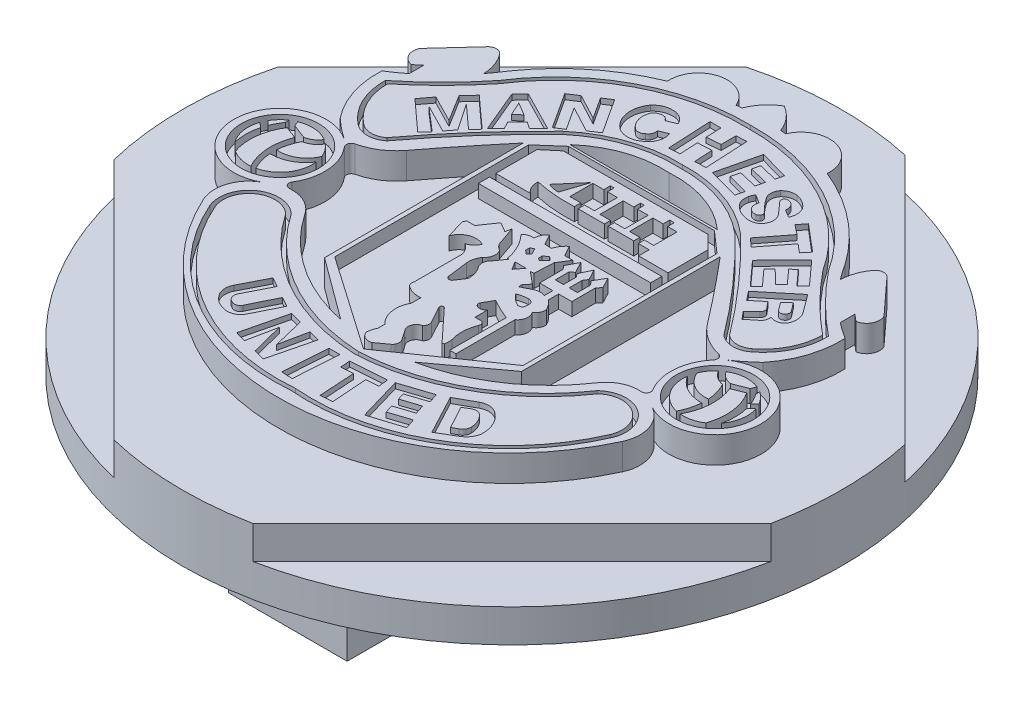
SolidWorks part; units mm, degrees
ref_plane "Ön Düzlem" through (0, 0, 0) normal (0, 0, 1) x (1, 0, 0)
ref_plane "Üst Düzlem" through (0, 0, 0) normal (0, 1, 0) x (1, 0, 0)
ref_plane "Sağ Düzlem" through (0, 0, 0) normal (1, 0, 0) x (0, 0, -1)
sketch "Çizim1" plane through (0, 0, 0) normal (0, 1, 0) x (1, 0, 0)
  line L0 (-150, -150) -> (150, -150)
  line L1 (-150, -150) -> (-150, 150)
  line L2 (-150, 150) -> (150, 150)
  line L3 (150, -150) -> (150, 150)
  line L4 (-150, -150) -> (150, 150) construction
  line L5 (-150, 150) -> (150, -150) construction
  point P0 (0, 0)
  dimension "D1" = 300
  dimension "D2" = 300
extrude "Yükseklik-Ekstrüzyon1" add sketch "Çizim1" along normal blind 35
sketch "Çizim2" plane through (0, 35, 0) normal (0, 1, 0) x (1, 0, 0)
  line L0 (0, 117.0614) -> (0, -131.4053) construction
  line L1 (-110, -110) -> (110, -110) construction
  line L2 (-110, -110) -> (-110, 110) construction
  line L3 (-110, 110) -> (110, 110) construction
  line L4 (110, -110) -> (110, 110) construction
  line L5 (-110, -110) -> (110, 110) construction
  line L6 (-110, 110) -> (110, -110) construction
  line L7 (0, 104.2196) -> (0, 158.9982)
  line L8 (0, 158.9982) -> (174.1845, 158.9982)
  line L9 (174.1845, 158.9982) -> (174.1845, -158.4564)
  line L10 (174.1845, -158.4564) -> (0, -158.4564)
  line L11 (0, -158.4564) -> (0, -87.5)
  line L12 (75.7238, 67.4719) -> (87.9979, 54.073)
  line L13 (84.3468, 47.103) -> (81.7641, 49.2839)
  line L14 (81.7641, 49.2839) -> (81.7641, 43.733)
  arc A0 (73.993, -19.7931) -> (72.5619, 9.9043) centre (82.5, -4.5) ccw
  arc A1 (-61.8718, 61.8718) -> (79.4822, -36.59) centre (0, 0) ccw
  arc A2 (79.4822, -36.59) -> (73.993, -19.7931) centre (67.6734, -31.1538) ccw
  arc A3 (7.3599, 95.5521) -> (9.4064, 95.3805) centre (2.1186, 20.7284) cw
  arc A4 (87.86, 39.4737) -> (81.7641, 43.733) centre (129.197, 105.1277) cw
  arc A5 (87.86, 39.4737) -> (80.1598, 15.9919) centre (53.3041, 37.8019) cw
  arc A6 (80.1598, 15.9919) -> (72.5619, 9.9043) centre (33.8885, 65.9578) cw
  arc A7 (9.4064, 95.3805) -> (30.2904, 90.2439) centre (19.441, 91.1557) cw
  arc A8 (0, 104.2196) -> (7.3599, 95.5521) centre (-8.4138, 89.6166) cw
  arc A9 (30.2904, 90.2439) -> (63.6389, 63.6389) centre (2.1186, 20.7284) cw
  arc A10 (67.6734, 57.8621) -> (70.963, 67.2595) centre (83.7021, 57.5257) cw
  arc A11 (70.963, 67.2595) -> (75.7238, 67.4719) centre (73.4323, 65.3728) cw
  arc A12 (87.9979, 54.073) -> (84.3468, 47.103) centre (83.5011, 51.9873) cw
  arc A13 (67.6734, 57.8621) -> (63.6389, 63.6389) centre (129.197, 105.1277) cw
  point P0 (0, 0)
  line M1 (150, -150) -> (150, 150)
  line M2 (150, 150) -> (-150, 150)
  line M4 (-150, -150) -> (150, -150)
  dimension "D5" = 35
  dimension "D6" = 175
  dimension "D7" = 26
  dimension "D1" = 220
  dimension "D2" = 220
  dimension "D3" = 4.5
  dimension "D4" = 82.5
extrude "Kes-Ekstrüzyon1" cut sketch "Çizim2" against normal blind 10 contours A13 A10 A11 L12 A12 L13 L14 A4 A5 A6 A0 A2 A1 L11 L7 A8 A3 A7 A9 M4 M1 M2 region at (3.3541, 35, -127.1098)
sketch "Çizim3" plane through (0, 35, 0) normal (0, 1, 0) x (1, 0, 0)
  line L0 (0, 60.4845) -> (0, 50.9362)
  line L1 (0, 50.9362) -> (27.9296, 50.9362)
  line L2 (37.3488, 42.6127) -> (37.3488, -32.762)
  line L3 (37.3488, -32.762) -> (13.9496, -50.0197)
  arc A0 (0, 60.4845) -> (27.9296, 50.9362) centre (2.6764, 22.691) cw
  arc A1 (55.2285, -22.4328) -> (13.9496, -50.0197) centre (0.3434, 15.0162) cw
  arc A2 (55.2285, -22.4328) -> (66.7327, -16.6811) centre (65.7274, -29.0514) cw
  arc A3 (69.9632, 7.3871) -> (68.9572, 10.393) centre (68.5479, 8.5847) ccw
  arc A4 (68.9572, 10.393) -> (57.05, 18.0417) centre (73.5332, 30.6092) cw
  arc A5 (37.3488, 42.6127) -> (57.05, 18.0417) centre (-455.6549, -372.867) cw
  arc A6 (66.7327, -16.6811) -> (68.3571, -14.0306) centre (66.8738, -14.9445) ccw
  arc A7 (68.3571, -14.0306) -> (69.9632, 7.3871) centre (83.9275, -4.4291) cw
extrude "Kes-Ekstrüzyon2" cut sketch "Çizim3" against normal blind 10
sketch "Çizim4" plane through (0, 35, 0) normal (0, 1, 0) x (1, 0, 0)
  line L0 (82.5, 1.0789) -> (87.1593, 2.8819)
  line L1 (80.9674, 2.8819) -> (86.3529, 4.9659)
  line L2 (86.3529, 4.9659) -> (87.1074, 6.8198)
  line L3 (89.2335, 4.222) -> (89.2335, 5.6993)
  line L4 (91.5097, 0) -> (93.0987, 1.5854)
  line L5 (92.2018, -2.119) -> (94.0821, -0.5988)
  arc A0 (70.3824, -2.9093) -> (79.7575, -16.4098) centre (82.5, -4.5) ccw
  circle A1 centre (82.5, -4.5) radius 14.6888
  arc A2 (79.7575, 1.0789) -> (81.8823, -6.409) centre (63.1981, -7.6655) cw
  arc A3 (79.7575, 1.0789) -> (74.5498, 4.7822) centre (80.9674, 8.2935) cw
  arc A4 (80.9674, 2.8819) -> (76.2386, 5.9957) centre (81.6657, 9.0899) cw
  arc A5 (81.8823, -6.409) -> (71.1371, 0) centre (80.8034, 3.9943) cw
  arc A6 (81.8823, -8.922) -> (70.3824, -2.9093) centre (81.4328, 4.222) cw
  arc A7 (82.5, 1.0789) -> (81.4038, -16.6723) centre (63.395, -6.6508) cw
  arc A8 (87.1593, 2.8819) -> (89.2335, -14.6993) centre (70.2409, -8.027) cw
  arc A9 (89.2335, 4.222) -> (91.5097, 0) centre (73.1727, -7.1617) cw
  arc A10 (81.8823, -8.922) -> (79.7575, -16.4098) centre (63.1981, -7.6655) cw
  arc A11 (92.2018, -2.119) -> (92.3057, -11.7947) centre (73.1727, -7.1617) cw
  arc A12 (92.3057, -11.7947) -> (94.0821, -0.5988) centre (82.5, -4.5) ccw
  arc A13 (81.4038, -16.6723) -> (89.2335, -14.6993) centre (82.5, -4.5) ccw
  arc A14 (74.5498, 4.7822) -> (71.1371, 0) centre (82.5, -4.5) ccw
  arc A15 (87.1074, 6.8198) -> (76.2386, 5.9957) centre (82.5, -4.5) ccw
  arc A16 (93.0987, 1.5854) -> (89.2335, 5.6993) centre (82.5, -4.5) ccw
extrude "Kes-Ekstrüzyon3" cut sketch "Çizim4" against normal blind 5
sketch "Çizim5" plane through (0, 35, 0) normal (0, 1, 0) x (1, 0, 0)
  line L0 (0, 91.5379) -> (0, 90.0374)
  line L1 (0, 65.6317) -> (0, 64.1304)
  line L2 (0, -57.1722) -> (0, -58.6739)
  line L3 (0, -81.2023) -> (0, -82.7077)
  arc A0 (0, 91.5379) -> (62.5307, 58.4876) centre (1.8857, 19.4269) cw
  arc A1 (84.0268, 36.9915) -> (62.5307, 58.4876) centre (173.773, 148.2339) cw
  arc A2 (84.0268, 36.9915) -> (74.573, 17.2499) centre (59.8349, 36.4421) cw
  arc A3 (74.573, 17.2499) -> (63.8811, 17.4485) centre (69.3515, 24.0494) cw
  arc A4 (0, 64.1304) -> (32.7048, 52.8449) centre (2.0165, 16.9426) cw
  arc A5 (32.7048, 52.8449) -> (63.8811, 17.4485) centre (-172.9235, -159.6954) cw
  arc A6 (0, 90.0374) -> (61.3126, 57.6086) centre (1.8857, 19.4269) cw
  arc A7 (82.5324, 36.2721) -> (61.3126, 57.6086) centre (173.773, 148.2339) cw
  arc A8 (82.5324, 36.2721) -> (73.6594, 18.4396) centre (59.8349, 36.4421) cw
  arc A9 (73.6594, 18.4396) -> (64.9701, 18.4968) centre (69.3515, 24.0494) cw
  arc A10 (33.7148, 53.9549) -> (64.9701, 18.4968) centre (-172.9235, -159.6954) cw
  arc A11 (0, 65.6317) -> (33.7148, 53.9549) centre (2.0165, 16.9426) cw
  arc A12 (58.0281, -24.6994) -> (0, -57.1722) centre (-3.5058, 17.1762) cw
  arc A13 (58.0281, -24.6994) -> (76.3367, -37.159) centre (65.8248, -32.9241) cw
  arc A14 (76.3367, -37.159) -> (0, -82.7077) centre (6.3669, -6.6362) cw
  arc A15 (59.1734, -25.6822) -> (0, -58.6739) centre (-3.5058, 17.1762) cw
  arc A16 (59.1734, -25.6822) -> (74.953, -36.5793) centre (65.8248, -32.9241) cw
  arc A17 (74.953, -36.5793) -> (0, -81.2023) centre (6.3669, -6.6362) cw
extrude "Kes-Ekstrüzyon4" cut sketch "Çizim5" against normal blind 5
mirror "Aynalama1" about plane through (0, 0, 0) normal (1, 0, 0) of "Kes-Ekstrüzyon4", "Kes-Ekstrüzyon3", "Kes-Ekstrüzyon2", "Kes-Ekstrüzyon1"
sketch "Çizim6" plane through (0, 35, 0) normal (0, 1, 0) x (1, 0, 0)
  line L1 (35.6973, -30.5495) -> (35.6973, 43.0345)
  line L2 (35.6973, 43.0345) -> (27.6949, 50.073)
  line L3 (27.6949, 50.073) -> (-27.6949, 50.073)
  line L4 (0, 0) -> (0, 50.073) construction
  line L5 (-35.6973, -30.5495) -> (-35.6973, 43.0345)
  line L6 (-35.6973, 43.0345) -> (-27.6949, 50.073)
  line L7 (-32.5816, 27.4101) -> (-32.5816, 43.0345)
  line L8 (-32.5816, 43.0345) -> (-27.1175, 47.6129)
  line L9 (-27.1175, 47.6129) -> (27.6949, 47.6129)
  line L10 (27.6949, 47.6129) -> (32.7594, 42.5484)
  line L11 (32.7594, 42.5484) -> (32.7594, 27.4101)
  line L12 (32.7594, 27.4101) -> (21.6068, 27.4101)
  line L13 (21.6068, 27.4101) -> (21.6068, 31.3958)
  line L14 (21.6068, 31.3958) -> (17.4791, 31.3958)
  line L15 (17.4791, 31.3958) -> (17.4791, 33.7073)
  line L16 (17.4791, 33.7073) -> (21.0289, 33.7073)
  line L17 (21.0289, 33.7073) -> (21.0289, 42.5484)
  line L18 (21.0289, 42.5484) -> (17.4791, 42.5484)
  line L19 (17.4791, 42.5484) -> (17.4791, 45.0807)
  line L20 (17.4791, 45.0807) -> (15.7454, 45.0807)
  line L21 (15.7454, 45.0807) -> (15.7454, 42.5484)
  line L22 (15.7454, 42.5484) -> (11.8654, 42.5484)
  line L23 (11.8654, 42.5484) -> (11.8654, 33.7073)
  line L24 (11.8654, 33.7073) -> (15.7454, 33.7073)
  line L25 (15.7454, 33.7073) -> (15.7454, 31.3958)
  line L26 (15.7454, 31.3958) -> (6.0866, 31.3958)
  line L27 (6.0866, 31.3958) -> (6.0866, 33.7073)
  line L28 (6.0866, 33.7073) -> (10.0766, 33.7073)
  line L29 (10.0766, 33.7073) -> (10.0766, 42.5484)
  line L30 (10.0766, 42.5484) -> (6.0866, 42.5484)
  line L31 (6.0866, 42.5484) -> (6.0866, 45.0807)
  line L32 (6.0866, 45.0807) -> (4.6191, 45.0807)
  line L33 (4.6191, 45.0807) -> (4.6191, 42.5484)
  line L34 (4.6191, 42.5484) -> (0.626, 42.5484)
  line L35 (0.626, 42.5484) -> (0.626, 33.9856)
  line L36 (0.626, 33.9856) -> (0.626, 33.7073)
  line L37 (0.626, 33.7073) -> (4.6191, 33.7073)
  line L38 (4.6191, 33.7073) -> (4.6191, 31.3958)
  line L39 (4.6191, 31.3958) -> (-5.3406, 31.3958)
  line L40 (-5.3406, 31.3958) -> (-5.3406, 33.8465)
  line L41 (-5.3406, 33.8465) -> (-1.577, 33.8465)
  line L42 (-1.577, 33.8465) -> (-1.577, 42.5484)
  line L43 (-1.577, 42.5484) -> (-5.3406, 42.5484)
  line L44 (-5.3406, 42.5484) -> (-5.3406, 45.0807)
  line L45 (-5.3406, 45.0807) -> (-6.7635, 45.0807)
  line L46 (-6.7635, 45.0807) -> (-6.7635, 42.5484)
  line L47 (-6.7635, 42.5484) -> (-10.8942, 42.5484)
  line L48 (-10.8942, 42.5484) -> (-10.8942, 33.8465)
  line L49 (-10.8942, 33.8465) -> (-6.7635, 33.8465)
  line L50 (-6.7635, 33.8465) -> (-6.7635, 31.3958)
  line L51 (-32.5816, 27.4101) -> (-19.4372, 27.4101)
  line L52 (-18.8002, 33.9856) -> (-11.4217, 42.5484)
  line L53 (-11.4217, 42.5484) -> (-14.5776, 33.1488)
  line L54 (-20.9353, -1.9012) -> (-23.028, 5.1542)
  line L55 (-32.5816, 25.0346) -> (32.7594, 25.0346)
  line L56 (-32.5816, 25.0346) -> (-32.5816, 20.8236)
  line L57 (-32.5816, 20.8236) -> (32.7594, 20.8236)
  line L58 (32.7594, 25.0346) -> (32.7594, 20.8236)
  line L59 (-23.028, 5.1542) -> (-22.4899, 6.2902)
  line L60 (-22.4899, 6.2902) -> (-19.4372, 6.2902)
  line L61 (-19.4372, 6.2902) -> (-15.3747, 12.1497)
  line L62 (-15.3747, 12.1497) -> (-11.7302, 10.0129)
  line L63 (-11.7302, 10.0129) -> (-11.2545, 12.1497)
  line L64 (-11.2545, 12.1497) -> (-8.7396, 4.8729)
  line L65 (-8.7396, -7.5608) -> (-7.7318, -15.1699)
  line L66 (-5.5404, -15.7177) -> (-3.3186, -12.4306)
  line L67 (-4.5097, -2.0077) -> (-1.8177, 1.8177)
  line L68 (-1.8177, 1.8177) -> (-2.4508, 1.8177)
  line L69 (-2.2142, 17.4209) -> (0, 13.4692)
  line L70 (0, 13.4692) -> (2.5928, 13.3318)
  line L71 (5.3491, 17.4209) -> (7.4713, 13.4692)
  line L72 (7.4713, 13.4692) -> (10.6011, 13.4692)
  line L73 (10.6011, 13.4692) -> (7.8603, 9.1968)
  line L74 (7.8603, 9.1968) -> (7.4713, 1.8177)
  line L75 (7.4713, 1.8177) -> (6.0866, 1.8177)
  line L76 (6.0866, 1.8177) -> (10.7337, -2.0077)
  line L77 (10.7337, -2.0077) -> (9.0154, -4.0951)
  line L78 (9.1527, -5.4691) -> (12.5683, -3.7017)
  line L79 (16.7607, -3.5331) -> (16.7607, -0.2789)
  line L80 (16.7607, -0.2789) -> (11.7213, -0.2789)
  line L81 (11.7213, -0.2789) -> (11.7213, 8.6628)
  line L82 (11.7213, 8.6628) -> (10.6011, 10.0129)
  line L83 (10.6011, 10.0129) -> (12.8268, 14.2738)
  line L84 (12.8268, 14.2738) -> (15.0316, 10.0129)
  line L85 (15.0316, 10.0129) -> (13.6782, 8.8901)
  line L86 (13.6782, 8.8901) -> (13.6782, 3.7222)
  line L87 (13.6782, 3.7222) -> (16.7626, 3.7222)
  line L88 (16.7626, 3.7222) -> (16.7626, 8.6619)
  line L89 (16.7626, 8.6619) -> (15.7474, 9.8855)
  line L90 (15.7474, 9.8855) -> (17.8609, 14.2728)
  line L91 (17.8609, 14.2728) -> (19.9544, 10.2271)
  line L92 (19.9544, 10.2271) -> (18.9502, 8.6619)
  line L93 (18.9502, 8.6619) -> (18.9502, 3.7222)
  line L94 (18.9502, 3.7222) -> (22.0786, 3.7222)
  line L95 (22.0786, 3.7222) -> (22.0786, 8.6619)
  line L96 (22.0786, 8.6619) -> (20.78, 10.2271)
  line L97 (20.78, 10.2271) -> (23.1519, 14.2728)
  line L98 (23.1519, 14.2728) -> (25.2454, 10.2271)
  line L99 (25.2454, 10.2271) -> (23.9569, 8.6619)
  line L100 (23.9569, 8.6619) -> (23.9569, -0.2789)
  line L101 (23.9569, -0.2789) -> (18.9502, -0.2789)
  line L102 (18.9502, -0.2789) -> (18.9502, -4.0951)
  line L103 (19.1333, -16.9923) -> (19.1333, -39.3968)
  line L104 (19.1333, -39.3968) -> (16.7845, -39.3968)
  line L105 (16.7845, -39.3968) -> (16.7845, -18.0047)
  line L106 (9.1527, -14.3283) -> (7.0465, -18.0047)
  line L107 (10.7336, -18.9486) -> (10.7336, -23.7673)
  line L108 (10.7336, -23.7673) -> (12.903, -23.7673)
  line L109 (12.7472, -38.2908) -> (1.7423, -26.4215)
  line L110 (0.626, -27.3608) -> (3.9137, -33.388)
  line L111 (2.0023, -41.7035) -> (4.3504, -45.1697)
  line L112 (3.7012, -48.5626) -> (-0.5329, -51.6429)
  line L113 (-4.0678, -45.8128) -> (-4.0678, -43.1848)
  line L114 (-5.9442, -31.2079) -> (-5.9442, -27.6327)
  line L115 (-12.4124, -23.7185) -> (-12.4124, -5.4691)
  line L116 (0, -55.3459) -> (-35.6973, -30.5495)
  line L117 (0, -55.3459) -> (35.6973, -30.5495)
  arc A0 (-6.7635, 31.3958) -> (-21.732, 32.6211) centre (-9.7576, 86.8596) cw
  arc A1 (-19.4372, 27.4101) -> (-21.732, 32.6211) centre (-15.9804, 32.0431) cw
  arc A2 (-14.5776, 33.1488) -> (-18.8002, 33.9856) centre (-14.9068, 42.5604) cw
  arc A3 (-20.9353, -1.9012) -> (-11.9069, 1.5667) centre (-14.8859, -4.164) cw
  arc A4 (-6.5727, 2.8365) -> (-8.7396, 4.8729) centre (-3.5561, 8.2174) cw
  arc A5 (-6.5727, 2.8365) -> (-7.4893, -2.6815) centre (-9.9894, 0.5689) cw
  arc A6 (-8.7396, -7.5608) -> (-7.4893, -2.6815) centre (-1.3306, -6.8595) cw
  arc A7 (-5.5404, -15.7177) -> (-7.7318, -15.1699) centre (-6.5681, -15.1718) cw
  arc A8 (-4.9621, -6.8595) -> (-3.3186, -12.4306) centre (-12.0993, -11.9931) cw
  arc A9 (-4.9621, -6.8595) -> (-4.5097, -2.0077) centre (-2.2142, -4.6688) cw
  arc A10 (-7.7318, 12.1497) -> (-2.4508, 1.8177) centre (-22.8138, -2.0749) cw
  arc A11 (-7.7318, 12.1497) -> (-4.0678, 13.3318) centre (-4.9068, 9.6627) cw
  arc A12 (-4.0678, 13.3318) -> (-2.2142, 17.4209) centre (1.0663, 13.4692) cw
  arc A13 (2.5928, 13.3318) -> (5.3491, 17.4209) centre (10.7337, 10.8179) cw
  arc A14 (9.1527, -5.4691) -> (9.0154, -4.0951) centre (10.0604, -4.6845) cw
  arc A15 (12.5683, -3.7017) -> (16.7607, -3.5331) centre (14.8448, -8.1009) cw
  arc A16 (18.9502, -4.0951) -> (21.7977, -7.8033) centre (11.8908, -12.4633) cw
  arc A17 (21.7977, -7.8033) -> (19.9544, -11.2995) centre (18.1521, -8.1153) cw
  arc A18 (19.9544, -11.2995) -> (19.1333, -16.9923) centre (16.7845, -13.7479) cw
  arc A19 (16.7845, -18.0047) -> (9.1527, -14.3283) centre (38.6907, 37.2295) cw
  arc A20 (10.7336, -18.9486) -> (7.5006, -19.6804) centre (8.7332, -17.6184) cw
  arc A21 (7.5006, -19.6804) -> (7.0465, -18.0047) centre (8.1422, -18.6071) cw
  arc A22 (12.903, -23.7673) -> (14.0714, -25.8765) centre (12.7472, -25.2318) cw
  arc A23 (13.6782, -35.3875) -> (14.0714, -25.8765) centre (27.8055, -31.2079) cw
  arc A24 (13.6782, -35.3875) -> (13.6782, -38.2908) centre (5.8594, -36.8392) cw
  arc A25 (13.6782, -38.2908) -> (12.7472, -38.2908) centre (13.2127, -37.7367) cw
  arc A26 (0.626, -27.3608) -> (1.7423, -26.4215) centre (1.2795, -27.0044) cw
  arc A27 (3.9137, -33.388) -> (3.4928, -36.4976) centre (2.0023, -34.7126) cw
  arc A28 (2.0023, -41.7035) -> (3.4928, -36.4976) centre (4.1169, -39.4926) cw
  arc A29 (4.3504, -45.1697) -> (3.7012, -48.5626) centre (2.215, -46.5197) cw
  arc A30 (-0.5329, -51.6429) -> (-4.9621, -49.3989) centre (-1.5866, -48.2296) cw
  arc A31 (-4.9621, -49.3989) -> (-4.0678, -45.8128) centre (2.6395, -49.39) cw
  arc A32 (-4.0678, -43.1848) -> (-5.9442, -31.2079) centre (2.7587, -35.9799) cw
  arc A33 (-5.9442, -27.6327) -> (-11.7277, -26.0886) centre (-6.9517, -19.8036) cw
  arc A34 (-11.7277, -26.0886) -> (-12.4124, -23.7185) centre (-10.4776, -24.4435) cw
  arc A35 (-15.3747, -1.4858) -> (-12.4124, -5.4691) centre (-18.869, -7.1776) cw
  arc A36 (-11.9069, 1.5667) -> (-15.3747, -1.4858) centre (-16.2343, 2.9868) cw
extrude "Kes-Ekstrüzyon5" cut sketch "Çizim6" against normal blind 5 contours A36 A3 L54 L59 L60 L61 L62 L63 L64 A4 A5 A6 L65 A7 L66 A8 A9 L67 L68 A10 A11 A12 L69 L57 L56 L55 L39 L40 L41 L42 L43 L44 L45 L46 L47 L48 L49 L50 A0 A1 L51 L7 L8 L9 L3 L6 L5 L116 | A2 L53 L52 region at (17.1223, 35, 41.902) region at (-14.9914, 35, -36.4596)
sketch "Çizim7" plane through (0, 35, 0) normal (0, 1, 0) x (1, 0, 0)
  line L0 (0.7036, 7.8454) -> (-0.3865, 10.0256)
  line L1 (-0.3865, 10.0256) -> (-1.6945, 9.3715)
  line L2 (-1.6945, 9.3715) -> (-1.6945, 7.8454)
  line L3 (-1.6945, 7.8454) -> (-0.3865, 6.7554)
  line L4 (-0.3865, 6.7554) -> (0.7036, 7.8454)
  line L5 (3.3409, 9.0761) -> (3.3409, 7.6344)
  line L6 (3.3409, 7.6344) -> (4.3606, 7.0015)
  line L7 (4.3606, 7.0015) -> (6.2946, 9.0761)
  line L8 (6.2946, 9.0761) -> (4.9904, 10.292)
  line L9 (4.9904, 10.292) -> (3.3409, 9.0761)
  line L10 (16.742, -8.8134) -> (16.742, -10.7481)
  line L11 (0.1374, 1.9898) -> (4.3606, 1.9898)
  line L12 (4.3606, 1.9898) -> (2.0006, -1.0407)
  line L13 (2.0006, -1.0407) -> (0.1374, 1.9898)
  arc A0 (10.7975, -8.3839) -> (14.8705, -7.5365) centre (15.1195, -18.945) cw
  arc A1 (14.8705, -7.5365) -> (16.742, -8.8134) centre (14.913, -9.4841) cw
  arc A2 (16.742, -10.7481) -> (14.553, -11.6091) centre (15.2849, -10.2569) cw
  arc A3 (14.553, -11.6091) -> (10.7975, -8.3839) centre (20.1152, -1.3333) cw
extrude "Kes-Ekstrüzyon6" cut sketch "Çizim7" against normal blind 2
sketch "Çizim8" plane through (0, 35, 0) normal (0, 1, 0) x (1, 0, 0)
  line L0 (-40.4775, -49.1576) -> (-36.879, -51.1821)
  line L1 (-28.564, -55.8599) -> (-33.5569, -65.9159)
  line L2 (-32.2727, -53.7735) -> (-37.1866, -63.8296)
  line L3 (-36.879, -51.1821) -> (-41.9041, -61.0943)
  line L4 (-40.4775, -49.1576) -> (-45.5273, -58.995)
  line L5 (-32.2727, -53.7735) -> (-28.564, -55.8599)
  line L6 (-40.7805, -64.5693) -> (-40.2475, -64.8442)
  line L7 (-40.2475, -64.8442) -> (-40.9873, -64.4813)
  line L8 (-29.3809, -74.0403) -> (-25.2986, -57.3447)
  line L9 (-25.2986, -57.3447) -> (-20.81, -58.4422)
  line L10 (-20.81, -58.4422) -> (-17.919, -70.3244)
  line L11 (-17.919, -70.3244) -> (-15.7409, -59.8675)
  line L12 (-15.7409, -59.8675) -> (-11.5928, -60.9784)
  line L13 (-11.5928, -60.9784) -> (-15.7409, -77.629)
  line L14 (-15.7409, -77.629) -> (-19.9002, -76.5928)
  line L15 (-19.9002, -76.5928) -> (-23.0507, -64.1974)
  line L16 (-23.0507, -64.1974) -> (-25.2986, -75.2479)
  line L17 (-25.2986, -75.2479) -> (-29.3809, -74.0403)
  line L18 (-7.9205, -78.3587) -> (-6.8023, -61.6601)
  line L19 (-6.8023, -61.6601) -> (-2.6493, -61.6601)
  line L20 (-2.6493, -61.6601) -> (-3.7859, -78.6356)
  line L21 (-3.7859, -78.6356) -> (-7.9205, -78.3587)
  line L22 (1.3637, -61.9288) -> (14.7656, -60.9784)
  line L23 (14.7656, -60.9784) -> (15.1312, -64.6902)
  line L24 (15.1312, -64.6902) -> (10.5259, -65.0168)
  line L25 (10.5259, -65.0168) -> (11.4818, -78.4971)
  line L26 (11.4818, -78.4971) -> (7.0139, -78.814)
  line L27 (7.0139, -78.814) -> (6.1869, -65.3245)
  line L28 (6.1869, -65.3245) -> (1.6244, -65.6043)
  line L29 (1.6244, -65.6043) -> (1.3637, -61.9288)
  line L30 (17.1288, -60.423) -> (28.8363, -56.5638)
  line L31 (28.8363, -56.5638) -> (29.9908, -60.0663)
  line L32 (29.9908, -60.0663) -> (22.287, -62.6057)
  line L33 (22.287, -62.6057) -> (23.1314, -65.1672)
  line L34 (23.1314, -65.1672) -> (29.9908, -62.906)
  line L35 (29.9908, -62.906) -> (31.1401, -66.3925)
  line L36 (31.1401, -66.3925) -> (24.0477, -68.7304)
  line L37 (24.0477, -68.7304) -> (25.0454, -71.757)
  line L38 (25.0454, -71.757) -> (32.7971, -69.2017)
  line L39 (32.7971, -69.2017) -> (34.0492, -73.0003)
  line L40 (34.0492, -73.0003) -> (21.9146, -76.8444)
  line L41 (21.9146, -76.8444) -> (17.1288, -60.423)
  line L42 (32.3892, -54.7835) -> (40.3451, -69.7455)
  line L43 (40.3451, -69.7455) -> (46.7976, -65.9159)
  line L44 (32.3892, -54.7835) -> (39.4126, -50.8839)
  line L45 (37.6681, -56.0504) -> (42.3029, -64.6093)
  line L46 (42.3029, -64.6093) -> (44.4135, -63.4664)
  line L47 (37.6681, -56.0504) -> (39.9966, -54.6365)
  line L48 (-60.9238, 26.1565) -> (-72.4633, 36.6262)
  line L49 (-72.4633, 36.6262) -> (-69.0244, 41.135)
  line L50 (-69.0244, 41.135) -> (-58.8605, 35.9384)
  line L51 (-58.8605, 35.9384) -> (-65.0505, 45.9495)
  line L52 (-65.0505, 45.9495) -> (-61.4005, 49.9725)
  line L53 (-61.4005, 49.9725) -> (-49.6728, 39.3322)
  line L54 (-49.6728, 39.3322) -> (-52.128, 36.6262)
  line L55 (-52.128, 36.6262) -> (-60.9238, 44.6065)
  line L56 (-60.9238, 44.6065) -> (-54.0711, 34.4845)
  line L57 (-54.0711, 34.4845) -> (-56.5259, 31.266)
  line L58 (-56.5259, 31.266) -> (-67.3514, 36.8008)
  line L59 (-67.3514, 36.8008) -> (-58.3138, 29.0333)
  line L60 (-58.3138, 29.0333) -> (-60.9238, 26.1565)
  line L61 (-48.9172, 40.6164) -> (-55.5367, 56.4356)
  line L62 (-55.5367, 56.4356) -> (-52.5684, 59.7072)
  line L63 (-52.5684, 59.7072) -> (-37.482, 51.9939)
  line L64 (-37.482, 51.9939) -> (-40.9499, 48.526)
  line L65 (-40.9499, 48.526) -> (-43.4499, 50.2599)
  line L66 (-43.4499, 50.2599) -> (-47.1775, 46.5323)
  line L67 (-47.1775, 46.5323) -> (-45.6785, 43.7347)
  line L68 (-45.6785, 43.7347) -> (-48.9172, 40.6164)
  line L69 (-36.879, 53.1563) -> (-45.6785, 66.6802)
  line L70 (-45.6785, 66.6802) -> (-41.9041, 69.136)
  line L71 (-41.9041, 69.136) -> (-32.2727, 64.0272)
  line L72 (-32.2727, 64.0272) -> (-37.482, 72.0333)
  line L73 (-37.482, 72.0333) -> (-34.2386, 74.1437)
  line L74 (-34.2386, 74.1437) -> (-25.6655, 60.9678)
  line L75 (-25.6655, 60.9678) -> (-29.3809, 58.5503)
  line L76 (-29.3809, 58.5503) -> (-39.2244, 63.7717)
  line L77 (-39.2244, 63.7717) -> (-33.6742, 55.2416)
  line L78 (-33.6742, 55.2416) -> (-36.879, 53.1563)
  line L79 (-14.3233, 78.2781) -> (-17.9194, 76.761)
  line L80 (-8.1316, 68.5423) -> (-8.9548, 85.0445)
  line L81 (-15.9239, 72.0333) -> (-12.6458, 73.4162)
  line L82 (-8.9548, 85.0445) -> (-4.8378, 85.0445)
  line L83 (-4.8378, 85.0445) -> (-4.5454, 79.1829)
  line L84 (-4.5454, 79.1829) -> (0.6515, 79.6556)
  line L85 (0.6515, 79.6556) -> (0.6515, 85.3183)
  line L86 (0.6515, 85.3183) -> (4.5734, 85.5139)
  line L87 (4.5734, 85.5139) -> (5.3864, 69.2167)
  line L88 (5.3864, 69.2167) -> (1.2247, 69.0091)
  line L89 (1.2247, 69.0091) -> (0.8778, 75.963)
  line L90 (0.8778, 75.963) -> (-4.3854, 75.7004)
  line L91 (-4.3854, 75.7004) -> (-4.0385, 68.7465)
  line L92 (-4.0385, 68.7465) -> (-8.1316, 68.5423)
  line L93 (11.9916, 84.4321) -> (8.2328, 68.7465)
  line L94 (8.2328, 68.7465) -> (19.8826, 65.6336)
  line L95 (19.8826, 65.6336) -> (20.7146, 68.7474)
  line L96 (20.7146, 68.7474) -> (12.83, 70.8542)
  line L97 (12.83, 70.8542) -> (13.6839, 74.0501)
  line L98 (13.6839, 74.0501) -> (20.7146, 72.3854)
  line L99 (20.7146, 72.3854) -> (21.4995, 75.7004)
  line L100 (21.4995, 75.7004) -> (14.4684, 77.3653)
  line L101 (14.4684, 77.3653) -> (15.1312, 80.1643)
  line L102 (15.1312, 80.1643) -> (22.287, 78.4699)
  line L103 (22.287, 78.4699) -> (22.9696, 81.3524)
  line L104 (22.9696, 81.3524) -> (11.9916, 84.4321)
  line L105 (23.8112, 69.632) -> (27.0544, 67.6663)
  line L106 (34.3831, 70.3286) -> (37.3604, 68.5423)
  line L107 (34.3831, 67.6663) -> (30.3926, 72.1896)
  line L108 (36.8981, 54.4946) -> (44.6573, 64.4396)
  line L109 (44.6573, 64.4396) -> (41.0116, 67.2841)
  line L110 (41.0116, 67.2841) -> (43.2639, 70.171)
  line L111 (43.2639, 70.171) -> (53.3841, 61.6159)
  line L112 (53.3841, 61.6159) -> (51.0905, 58.9027)
  line L113 (51.0905, 58.9027) -> (47.8809, 61.6159)
  line L114 (47.8809, 61.6159) -> (40.0853, 51.6242)
  line L115 (40.0853, 51.6242) -> (36.8981, 54.4946)
  line L116 (52.9141, 38.4271) -> (44.6573, 47.5569)
  line L117 (44.6573, 47.5569) -> (55.7635, 58.9027)
  line L118 (55.7635, 58.9027) -> (63.8397, 49.9725)
  line L119 (63.8397, 49.9725) -> (61.4752, 47.5569)
  line L120 (61.4752, 47.5569) -> (56.3447, 53.2298)
  line L121 (56.3447, 53.2298) -> (54.4242, 51.4929)
  line L122 (54.4242, 51.4929) -> (59.1973, 46.215)
  line L123 (59.1973, 46.215) -> (56.9743, 43.944)
  line L124 (56.9743, 43.944) -> (51.8543, 48.9558)
  line L125 (51.8543, 48.9558) -> (49.7359, 46.7916)
  line L126 (49.7359, 46.7916) -> (55.2122, 40.7362)
  line L127 (55.2122, 40.7362) -> (52.9141, 38.4271)
  line L128 (52.9141, 38.4271) -> (52.8662, 38.4183)
  line L129 (54.0631, 36.6262) -> (66.3709, 46.7916)
  line L130 (66.3709, 46.7916) -> (71.3833, 40.0292)
  line L131 (65.2501, 28.7968) -> (62.0429, 26.159)
  line L132 (62.0429, 26.159) -> (59.679, 29.0333)
  line L133 (59.679, 29.0333) -> (62.891, 32.142)
  line L134 (63.1218, 34.4845) -> (61.1248, 36.9054)
  line L135 (61.1248, 36.9054) -> (56.7118, 33.2653)
  line L136 (56.7118, 33.2653) -> (54.0631, 36.6262)
  line L137 (-48.9172, 49.7023) -> (-51.2952, 54.8735)
  line L138 (-51.2952, 54.8735) -> (-46.4642, 51.9939)
  line L139 (-46.4642, 51.9939) -> (-48.9172, 49.7023)
  line L140 (63.8397, 38.9882) -> (66.3406, 41.3245)
  line L141 (66.3406, 41.3245) -> (68.5807, 38.4271)
  line L142 (63.8397, 38.9882) -> (66.136, 35.9384)
  arc A0 (-33.5569, -65.9159) -> (-40.3024, -68.4265) centre (-38.2673, -63.5772) cw
  arc A1 (-44.4165, -65.8319) -> (-45.5273, -58.995) centre (-40.3355, -61.6601) cw
  arc A2 (-40.3024, -68.4265) -> (-44.4165, -65.8319) centre (-38.4804, -60.9784) cw
  arc A3 (-37.1866, -63.8296) -> (-40.2475, -64.8442) centre (-39.2135, -62.8391) cw
  arc A4 (-40.7805, -64.5693) -> (-41.9041, -61.0943) centre (-39.5927, -62.2661) cw
  arc A5 (39.4126, -50.8839) -> (45.2457, -50.9382) centre (42.2813, -56.0504) cw
  arc A6 (50.3009, -61.0568) -> (46.7976, -65.9159) centre (43.4836, -59.8341) cw
  arc A7 (45.2457, -50.9382) -> (50.3009, -61.0568) centre (39.084, -60.3387) cw
  arc A8 (39.9966, -54.6365) -> (43.1499, -54.5494) centre (41.6496, -57.3587) cw
  arc A9 (46.1218, -60.4091) -> (44.4135, -63.4664) centre (42.8559, -60.5901) cw
  arc A10 (43.1499, -54.5494) -> (46.1218, -60.4091) centre (37.9679, -60.8611) cw
  arc A11 (-12.6458, 73.4162) -> (-15.2982, 65.7824) centre (-18.5195, 71.1793) cw
  arc A12 (-15.9239, 72.0333) -> (-17.2125, 68.8526) centre (-18.564, 71.2516) cw
  arc A13 (-17.2125, 68.8526) -> (-21.1135, 68.8526) centre (-19.163, 70.7609) cw
  arc A14 (-21.1135, 68.8526) -> (-23.051, 76.436) centre (-16.5833, 74.0492) cw
  arc A15 (-23.051, 76.436) -> (-19.1633, 78.076) centre (-20.0202, 74.6794) cw
  arc A16 (-19.1633, 78.076) -> (-17.9194, 76.761) centre (-20.0799, 75.963) cw
  arc A17 (-15.2982, 65.7824) -> (-24.8338, 66.6802) centre (-19.5784, 71.4105) cw
  arc A18 (-24.8338, 66.6802) -> (-25.6655, 79.1829) centre (-17.7505, 73.4304) cw
  arc A19 (-25.6655, 79.1829) -> (-18.534, 81.669) centre (-19.8736, 74.0403) cw
  arc A20 (-18.534, 81.669) -> (-14.3233, 78.2781) centre (-19.5019, 76.1574) cw
  arc A21 (22.9696, 67.6663) -> (23.8112, 69.632) centre (27.7787, 66.7702) cw
  arc A22 (23.8112, 63.5152) -> (22.9696, 67.6663) centre (27.7944, 66.4837) cw
  arc A23 (30.1282, 60.0349) -> (23.8112, 63.5152) centre (31.1809, 69.4185) cw
  arc A24 (33.6388, 60.739) -> (30.1282, 60.0349) centre (30.7832, 65.8731) cw
  arc A25 (35.5854, 64.0272) -> (33.6388, 60.739) centre (30.5166, 64.8076) cw
  arc A26 (34.3831, 67.6663) -> (35.5854, 64.0272) centre (30.7256, 64.4396) cw
  arc A27 (30.3926, 72.1896) -> (31.1401, 74.0501) centre (31.4982, 72.8258) cw
  arc A28 (31.1401, 74.0501) -> (34.3831, 71.6882) centre (31.536, 71.1865) cw
  arc A29 (34.3831, 71.6882) -> (34.3831, 70.3286) centre (31.8433, 71.0084) cw
  arc A30 (37.1337, 74.0501) -> (37.3604, 68.5423) centre (32.0402, 71.082) cw
  arc A31 (31.6895, 77.3653) -> (37.1337, 74.0501) centre (30.1032, 68.6324) cw
  arc A32 (27.0544, 75.7004) -> (31.6895, 77.3653) centre (31.006, 71.9834) cw
  arc A33 (26.5913, 71.0084) -> (27.0544, 75.7004) centre (30.5055, 72.991) cw
  arc A34 (30.7832, 65.8731) -> (26.5913, 71.0084) centre (51.364, 86.9512) cw
  arc A35 (30.7832, 65.8731) -> (30.2991, 63.2275) centre (30.1, 64.631) cw
  arc A36 (30.2991, 63.2275) -> (26.7843, 66.3442) centre (29.8662, 66.2795) cw
  arc A37 (26.7843, 66.3442) -> (27.0544, 67.6663) centre (34.9633, 65.3622) cw
  arc A38 (71.3833, 40.0292) -> (71.8571, 33.4642) centre (66.4513, 36.3736) cw
  arc A39 (71.8571, 33.4642) -> (66.885, 32.4095) centre (68.7662, 35.7881) cw
  arc A40 (66.885, 32.4095) -> (65.2501, 28.7968) centre (63.5479, 31.7434) cw
  arc A41 (63.1218, 34.4845) -> (62.891, 32.142) centre (61.841, 33.428) cw
  arc A42 (68.5807, 38.4271) -> (66.136, 35.9384) centre (67.3107, 37.2295) cw
extrude "Kes-Ekstrüzyon7" cut sketch "Çizim8" against normal blind 2 contours L6 A4 L3 L0 L4 A1 A2 A0 L1 L5 L2 A3 | L17 L16 L15 L14 L13 L12 L11 L10 L9 L8 | L41 L40 L39 L38 L37 L36 L35 L34 L33 L32 L31 L30 | A7 A5 L44 L42 L43 A6 A8 A10 A9 L46 L45 L47 | L60 L59 L58 L57 L56 L55 L54 L53 L52 L51 L50 L49 L48 | L68 L67 L66 L65 L64 L63 L62 L61 L138 L139 L137 | L78 L77 L76 L75 L74 L73 L72 L71 L70 L69 | A20 A19 A18 A17 A11 L81 A12 A13 A14 A15 A16 L79 | L92 L91 L90 L89 L88 L87 L86 L85 L84 L83 L82 L80 | L103 L104 L93 L94 L95 L96 L97 L98 L99 L100 L101 L102 | A36 A37 L105 A21 A22 A23 A24 A25 A26 L107 A27 A28 A29 L106 A30 A31 A32 A33 A34 A35 | L115 L114 L113 L112 L111 L110 L109 L108 | L134 A41 L133 L132 L131 A40 A39 A38 L130 L129 L136 L135 L141 A42 L142 L140 | L127 L126 L125 L124 L123 L122 L121 L120 L119 L118 L117 L116 | L18 L19 L20 L21 | L27 L28 L29 L22 L23 L24 L25 L26 region at (-38.8077, 35, 50.4) region at (-20.4922, 35, 67.4402) region at (24.7984, 35, 66.977) region at (36.0299, 35, 53.066) region at (-66.4721, 35, -31.6355) region at (-51.9845, 35, -48.6274) region at (-35.6728, 35, -63.7553) region at (-16.2115, 35, -77.7334) region at (-1.7905, 35, -77.1027) region at (15.0066, 35, -75.1743) region at (30.5316, 35, -68.5917) region at (44.6147, 35, -61.0482) region at (53.7858, 35, -49.3415) region at (64.4301, 35, -36.8823)
sketch "Çizim9" plane through (0, 25, 0) normal (0, 1, 0) x (1, 0, 0)
  line L1 (-182.0932, 158.5045) -> (184.9699, 158.5045)
  line L2 (-182.0932, 158.5045) -> (-182.0932, -159.0799)
  line L3 (-182.0932, -159.0799) -> (184.9699, -159.0799)
  line L4 (184.9699, 158.5045) -> (184.9699, -159.0799)
  circle A0 centre (2.0006, -1.0407) radius 125
extrude "Kes-Ekstrüzyon8" cut sketch "Çizim9" against normal through all both and the other way through all
sketch "Çizim10" plane through (0, 25, 0) normal (0, 1, 0) x (1, 0, 0)
  line L0 (-150, 0) -> (0, 150)
  line L1 (0, 150) -> (150, 0)
  line L2 (150, 0) -> (0, -150)
  line L3 (0, -150) -> (-150, 0)
  line L5 (-279.3657, 207.6841) -> (314.5022, 207.6841)
  line L6 (-279.3657, 207.6841) -> (-279.3657, -253.1261)
  line L7 (-279.3657, -253.1261) -> (314.5022, -253.1261)
  line L8 (314.5022, 207.6841) -> (314.5022, -253.1261)
  dimension "D1" = 300
extrude "Kes-Ekstrüzyon9" cut sketch "Çizim10" against normal blind 12.5
scale "Scale1" scale about centroid uniform scaling no x scale factor 0.1 y scale factor 0.1 z scale factor 0.1
sketch "Sketch1" plane through (0, 13.1368, 0) normal (0, -1, 0) x (-1, 0, 0)
  line L0 (-13.7705, 0.2806) -> (11.2295, 0.2806) construction
  line L1 (-1.2705, 0.2806) -> (-1.2705, 12.7806) construction
  line L2 (-3.5205, -8.2194) -> (0.9795, -5.2194) construction
  line L3 (-3.5205, 5.7806) -> (0.9795, 5.7806)
  line L4 (-3.5205, 5.7806) -> (-3.5205, 8.7806)
  line L5 (-3.5205, 8.7806) -> (0.9795, 8.7806)
  line L6 (0.9795, 5.7806) -> (0.9795, 8.7806)
  line L7 (-3.5205, 5.7806) -> (0.9795, 8.7806) construction
  line L8 (-3.5205, 8.7806) -> (0.9795, 5.7806) construction
  line L9 (-3.5205, -5.2194) -> (0.9795, -8.2194) construction
  line L10 (0.9795, -5.2194) -> (0.9795, -8.2194)
  line L11 (-3.5205, -8.2194) -> (0.9795, -8.2194)
  line L12 (-3.5205, -5.2194) -> (-3.5205, -8.2194)
  line L13 (-3.5205, -5.2194) -> (0.9795, -5.2194)
  circle A0 centre (-1.2705, 0.2806) radius 12.5 construction
  point P7 (-1.2705, 7.2806)
  point P16 (-1.2705, -6.7194)
  dimension "D1" = 3
  dimension "D2" = 4.5
  dimension "D3" = 5.5
extrude "Boss-Extrude1" add sketch "Sketch1" along normal blind 4
